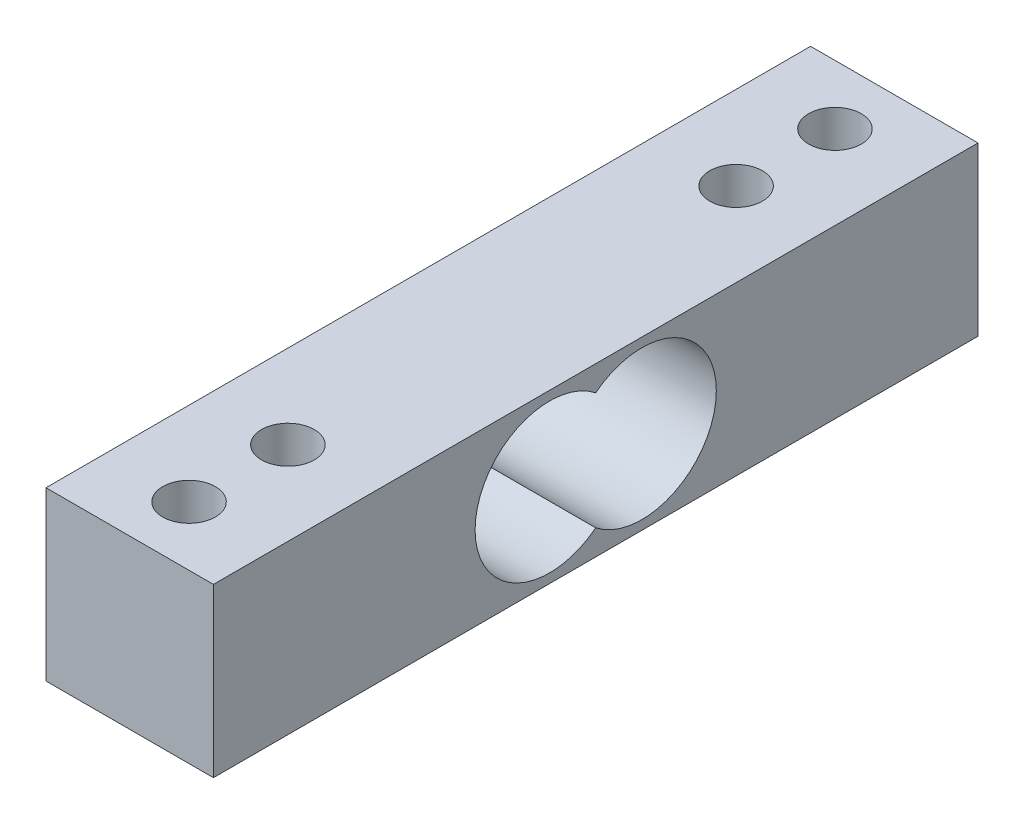
SolidWorks part; units mm, degrees
ref_plane "Plan de face" through (0, 0, 0) normal (0, 0, 1) x (1, 0, 0)
ref_plane "Plan de dessus" through (0, 0, 0) normal (0, 1, 0) x (1, 0, 0)
ref_plane "Plan de droite" through (0, 0, 0) normal (1, 0, 0) x (0, 0, -1)
sketch "Esquisse1" plane through (0, 0, 0) normal (0, 0, 1) x (1, 0, 0)
  line L0 (0, 19.2175) -> (0, -29.9729) construction
  line L1 (-6.35, 6.35) -> (6.35, 6.35)
  line L2 (-6.35, 6.35) -> (-6.35, -6.35)
  line L3 (-6.35, -6.35) -> (6.35, -6.35)
  line L4 (6.35, 6.35) -> (6.35, -6.35)
  line L5 (-22.701, 0) -> (33.2907, 0) construction
  dimension "D1" = 12.7
extrude "Boss.-Extru.1" add sketch "Esquisse1" against normal mid plane 58
sketch "Esquisse2" plane through (0, 6.35, 0) normal (0, 1, 0) x (1, 0, 0)
  line L0 (0, 29) -> (0, -29) construction
  line L1 (6.35, 29) -> (-6.35, 29) construction
  line L2 (6.35, -29) -> (-6.35, -29) construction
  line L3 (-6.35, 0) -> (6.35, 0) construction
  line L4 (-6.35, 29) -> (-6.35, -29) construction
  line L5 (6.35, 29) -> (6.35, -29) construction
  circle A0 centre (0, 24.5) radius 2
  circle A1 centre (0, 17) radius 2
  circle A2 centre (0, -17) radius 2
  circle A3 centre (0, -24.5) radius 2
  dimension "D3" = 4
  dimension "7" = 7.5
  dimension "D2" = 34
extrude "Enlèv. mat.-Extru.1" cut sketch "Esquisse2" against normal through all
sketch "Esquisse3" plane through (6.35, 0, 0) normal (1, 0, 0) x (0, 0, -1)
  line L0 (-29, 0) -> (29, 0) construction
  line L1 (-29, -6.35) -> (-29, 6.35) construction
  line L2 (29, -6.35) -> (29, 6.35) construction
  line L3 (0, 6.35) -> (0, -6.35) construction
  line L4 (29, 6.35) -> (-29, 6.35) construction
  line L5 (29, -6.35) -> (-29, -6.35) construction
  arc A0 (0, 4.4354) -> (0, -4.4354) centre (-3.5, 0) ccw
  arc A1 (0, -4.4354) -> (0, 4.4354) centre (3.5, 0) ccw
  dimension "D2" = 11.3
  dimension "D1" = 7
extrude "Enlèv. mat.-Extru.2" cut sketch "Esquisse3" against normal through all
ref_axis "Axe1" through (0, 0, -32.45) along (0, 0, 1)
ref_axis "Axe2" through (10.725, 0, 0) along (-1, 0, 0)
ref_plane "Plan1" through (0, 0, 24.5) normal (0, 0, -1) x (-1, 0, 0)
ref_plane "Plan2" through (0, 0, 17) normal (0, 0, -1) x (-1, 0, 0)
ref_plane "Plan3" through (0, 0, 20.75) normal (0, 0, -1) x (-1, 0, 0)
ref_axis "Axe3" through (0, -27.7396, 20.75) along (0, 1, 0)
ref_plane "Plan4" through (0, 0, -17) normal (0, 0, -1) x (-1, 0, 0)
ref_plane "Plan5" through (0, 0, -24.5) normal (0, 0, -1) x (-1, 0, 0)
ref_plane "Plan6" through (0, 0, -20.75) normal (0, 0, -1) x (-1, 0, 0)
ref_axis "Axe4" through (0, 50.0677, -20.75) along (0, -1, 0)
